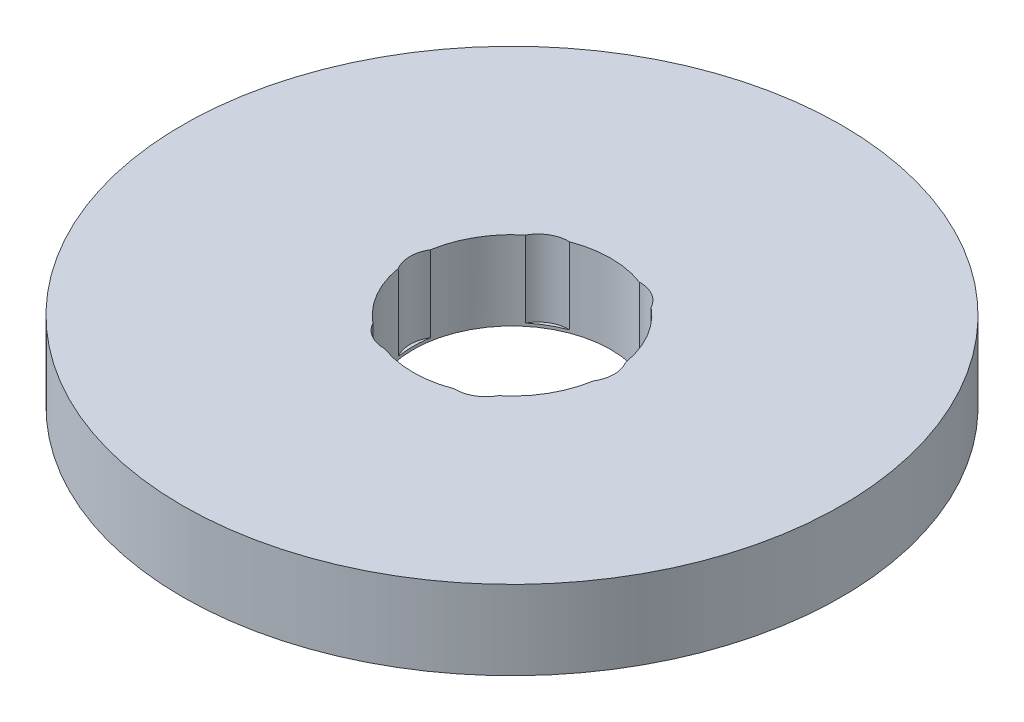
SolidWorks part; units mm, degrees
ref_plane "Front Plane" through (0, 0, 0) normal (0, 0, 1) x (1, 0, 0)
ref_plane "Top Plane" through (0, 0, 0) normal (0, 1, 0) x (1, 0, 0)
ref_plane "Right Plane" through (0, 0, 0) normal (1, 0, 0) x (0, 0, -1)
sketch "Sketch1" plane through (0, 0, 0) normal (0, 1, 0) x (1, 0, 0)
  circle A0 centre (0, 0) radius 75
  dimension "FLANGE_OD" = 150
extrude "Boss-Extrude1" add sketch "Sketch1" along normal blind 18
sketch "Sketch2" plane through (0, 0, 0) normal (0, 1, 0) x (1, 0, 0)
  circle A0 centre (0, 0) radius 22.5
  dimension "BORE_D" = 45
extrude "Cut-Extrude1" cut sketch "Sketch2" along normal through all
sketch "Sketch3" plane through (0, 18, 0) normal (0, 1, 0) x (1, 0, 0)
  circle A0 centre (0, 0) radius 16.188 construction
  circle A1 centre (-16.188, 0) radius 7.0386
  dimension "BOLT_D" = 14.0772
  dimension "BOLT_PCD" = 32.376
extrude "Cut-Extrude2" cut sketch "Sketch3" against normal blind 17.3474
pattern_circular "CirPattern1" count 6 over 360 about axis through (0, 0, 0) along (0, 1, 0) of "Cut-Extrude2"
